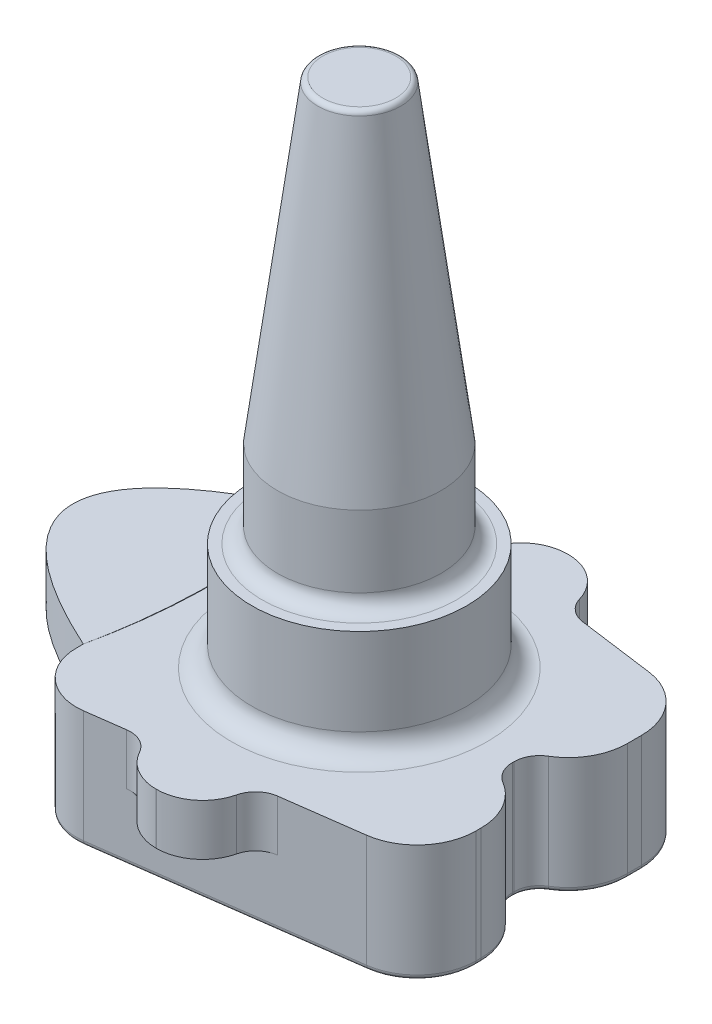
SolidWorks part; units mm, degrees
ref_plane "Plano frontal" through (0, 0, 0) normal (0, 0, 1) x (1, 0, 0)
ref_plane "Plano superior" through (0, 0, 0) normal (0, 1, 0) x (1, 0, 0)
ref_plane "Plano direito" through (0, 0, 0) normal (1, 0, 0) x (0, 0, -1)
sketch "Esboço1" plane through (0, 0, 0) normal (0, 0, 1) x (1, 0, 0)
  line L0 (17.3846, 86.7357) -> (17.3846, -75.0236) construction
  line L1 (17.3846, 86.7357) -> (25.3846, 86.7357)
  line L2 (25.3846, 86.7357) -> (33.3846, 24.7357)
  line L3 (33.3846, 24.7357) -> (33.3846, 7.7357)
  line L4 (33.3846, 7.7357) -> (38.3846, 7.7357)
  line L5 (38.3846, 7.7357) -> (38.3846, -13.2643)
  line L6 (38.3846, -13.2643) -> (97.3846, -13.2643)
  line L7 (97.3846, -13.2643) -> (97.3846, -36.2643)
  line L8 (97.3846, -36.2643) -> (17.3846, -36.2643)
  line L9 (17.3846, 86.7357) -> (17.3846, -36.2643)
  dimension "D1" = 8
  dimension "D2" = 80
  dimension "D3" = 21
  dimension "D4" = 16
  dimension "D5" = 23
  dimension "D6" = 44
  dimension "D7" = 61
  dimension "D8" = 123
revolve "Revolução1" add sketch "Esboço1" angle 360 about L0
sketch "Esboço2" plane through (0, -36.2643, 0) normal (0, -1, 0) x (1, 0, 0)
  line L0 (-62.6154, 0) -> (17.3846, 0) construction
  line L1 (56.3846, 26.25) -> (56.3846, -26.25)
  line L2 (-13.6154, 0) -> (17.3846, 0) construction
  line L3 (-13.6154, 35.75) -> (-13.6154, -35.75)
  line L4 (-13.6154, 35.75) -> (56.3846, 26.25)
  line L5 (-13.6154, -35.75) -> (56.3846, -26.25)
  circle A0 centre (17.3846, 0) radius 80 construction
  dimension "D1" = 52.5
  dimension "D2" = 31
  dimension "D3" = 71.5
extrude "Corte-extrusão2" cut sketch "Esboço2" against normal through all flip side to cut
sketch "Esboço3" plane through (0, -36.2643, 0) normal (0, -1, 0) x (1, 0, 0)
  line L0 (-13.6154, 0) -> (-117.6154, 0) construction
  line L1 (-13.6154, 35.75) -> (-13.6154, -35.75) construction
  line L2 (-13.6154, 0) -> (-11.1154, 0) construction
  circle A0 centre (-117.6154, 0) radius 106.5
  dimension "D1" = 2.5
  dimension "D2" = 104
extrude "Corte-extrusão3" cut sketch "Esboço3" against normal through all
fillet "Filete1" radius 10 2 edges at (-13.6154, -24.7643, -35.75) (-13.6154, -24.7643, 35.75)
sketch "Esboço4" plane through (0, -36.2643, 0) normal (0, -1, 0) x (1, 0, 0)
  line L0 (56.3846, -4.25) -> (48.3846, -4.25)
  line L1 (56.3846, -26.25) -> (56.3846, 26.25) construction
  line L2 (56.3846, 4.25) -> (48.3846, 4.25)
  line L3 (-11.1154, 0) -> (75.7968, 0) construction
  line L4 (48.3846, 4.25) -> (48.3846, -4.25)
  line L5 (48.3846, -4.25) -> (48.384, -4.0765)
  line L6 (56.3846, 4.25) -> (56.3846, -4.25)
  arc A0 (-13.6154, -22.9401) -> (-13.6154, 22.9401) centre (-117.6154, 0) ccw construction
  line M4 (56.3846, -26.25) -> (56.3846, 26.25)
  dimension "D2" = 8
extrude "Corte-extrusão4" cut sketch "Esboço4" against normal through all contours L4 L3 L6 L2 | L3 L4 L0 M4 region at (52.3846, -36.2643, -2.125) region at (52.3846, -36.2643, 2.125)
fillet "Filete2" radius 11.5 1 edges at (56.3846, -24.7643, 26.25)
fillet "Filete3" radius 11.5 1 edges at (56.3846, -24.7643, 4.25)
fillet "Filete4" radius 5 1 edges at (48.3846, -24.7643, 4.25)
fillet "Filete5" radius 5 1 edges at (48.3846, -24.7643, -4.25)
fillet "Filete6" radius 11.5 2 edges at (56.3846, -24.7643, -26.25) (56.3846, -24.7643, -4.25)
fillet "Filete7" radius 4 1 edges at (-3.6154, -13.2643, 0)
fillet "Filete8" radius 3 1 edges at (1.3846, 7.7357, 0)
fillet "Filete10" radius 1 16 edges at (-10.1938, -36.2643, -31.8327) (-13.6154, -36.2643, -23.6207) (-11.1154, -36.2643, 0) (-13.6154, -36.2643, 23.6207) (-10.1938, -36.2643, 31.8327) (22.0803, -36.2643, 30.9056) (53.5459, -36.2643, 23.7705) (56.3846, -36.2643, 15.7049) (54.8941, -36.2643, 9.5422) (49.0327, -36.2643, 3.5241) (48.3846, -36.2643, 0.9062) (49.0327, -36.2643, -1.7118) (54.8941, -36.2643, -7.7299) (56.3846, -36.2643, -14.7987) (53.5459, -36.2643, -23.7705) (22.0803, -36.2643, -30.9056)
sketch "Esboço5" plane through (0, -36.2643, 0) normal (0, -1, 0) x (1, 0, 0)
  line L0 (-10.1154, 0) -> (47.3846, 0.75) construction
  arc A0 (-12.6154, -23.0489) -> (-12.6154, 23.0489) centre (-117.6154, 0) ccw construction
  circle A1 centre (18.6346, 0.375) radius 20.5
  dimension "D1" = 41
extrude "Corte-extrusão6" cut sketch "Esboço5" against normal blind 2.5
chamfer "Chanfro1" distance 2 angle 45 1 edges at (39.1346, -33.7643, 0.375)
sketch "Esboço6" plane through (0, -33.7643, 0) normal (0, -1, 0) x (1, 0, 0)
  line L0 (0, 0) -> (18.6346, 0.375) construction
  line L1 (13.6346, 10.375) -> (23.6346, -9.625) construction
  line L2 (13.6346, 10.375) -> (23.6346, 10.375)
  line L3 (13.6346, 10.375) -> (13.6346, -9.625)
  line L4 (13.6346, -9.625) -> (23.6346, -9.625)
  line L5 (23.6346, 10.375) -> (23.6346, -9.625)
  dimension "D1" = 10
  dimension "D2" = 20
extrude "Corte-extrusão7" cut sketch "Esboço6" against normal blind 10
chamfer "Chanfro2" distance 1 angle 45 4 edges at (18.6346, -33.7643, -9.625) (23.6346, -33.7643, 0.375) (13.6346, -33.7643, 0.375) (18.6346, -33.7643, 10.375)
sketch "Esboço7" plane through (0, -36.2643, 0) normal (0, -1, 0) x (1, 0, 0)
  line L0 (18.6346, 0.375) -> (18.6346, 40.375) construction
  line L3 (9.1423, 40.375) -> (27.1423, 40.375)
  line L4 (9.1423, 40.375) -> (9.1423, 32.6615)
  line L5 (-2.2705, 34.2103) -> (46.4312, 27.6008) construction
  line L6 (9.1423, 32.6615) -> (27.1423, 30.2186)
  line L7 (27.1423, 30.2186) -> (27.1423, 40.375)
  line L8 (18.6346, 0.375) -> (71.2498, 0.375) construction
  line L9 (18.6346, 0.375) -> (18.6346, -39.625) construction
  line L10 (9.6346, -39.625) -> (27.6346, -39.625)
  line L11 (9.6346, -39.625) -> (9.6346, -32.5946)
  line L12 (46.4312, -27.6008) -> (-2.2705, -34.2103) construction
  line L13 (9.6346, -32.5946) -> (27.6346, -30.1518)
  line L14 (27.6346, -30.1518) -> (27.6346, -39.625)
  dimension "D1" = 40
  dimension "D2" = 18
  dimension "D3" = 40
  dimension "D4" = 18
extrude "Ressalto-extrusão2" add sketch "Esboço7" against normal blind 23
sketch "Esboço8" plane through (0, -36.2643, 0) normal (0, -1, 0) x (1, 0, 0)
  line L1 (27.1423, 40.375) -> (9.1423, 40.375) construction
  line L2 (9.1423, 40.375) -> (9.1423, 32.6615) construction
  line L3 (9.1423, 40.375) -> (27.1423, 40.375)
  line L5 (27.1423, 30.2186) -> (27.1423, 40.375) construction
  line L6 (27.1423, 30.2186) -> (9.1423, 32.6615)
  line L8 (9.1423, 32.6615) -> (9.1423, 44.4525)
  line L9 (9.1423, 44.4525) -> (27.1423, 44.2335)
  line L10 (27.1423, 44.2335) -> (27.1423, 30.2186)
  line M1 (9.1423, 40.375) -> (9.1423, 32.6615)
  line M2 (9.1423, 32.6615) -> (27.1423, 30.2186)
  line M3 (27.1423, 30.2186) -> (27.1423, 40.375)
  line M4 (27.1423, 40.375) -> (9.1423, 40.375)
extrude "Corte-extrusão10" cut sketch "Esboço8" against normal blind 13 contours M4 M1 M2 M3 region at (18.5524, -36.2643, 35.8797)
sketch "Esboço9" plane through (0, -36.2643, 0) normal (0, -1, 0) x (1, 0, 0)
  line L0 (9.6346, -32.5946) -> (9.6346, -45.9068)
  line L1 (27.6346, -30.1518) -> (27.9806, -45.9068)
  line L2 (27.9806, -45.9068) -> (9.6346, -45.9068)
  line L3 (9.6346, -32.5946) -> (27.6346, -30.1518)
extrude "Corte-extrusão11" cut sketch "Esboço9" against normal blind 13
fillet "Filete11" radius 9 2 edges at (9.1423, -18.2643, 40.375) (27.1423, -18.2643, 40.375)
fillet "Filete12" radius 5 1 edges at (27.1423, -18.2643, 30.2186)
fillet "Filete15" radius 5 1 edges at (9.1423, -18.2643, 32.6615)
fillet "Filete16" radius 9 2 edges at (9.6346, -18.2643, -39.625) (27.6346, -18.2643, -39.625)
fillet "Filete17" radius 5 1 edges at (27.6346, -18.2643, -30.1518)
fillet "Filete18" radius 5 1 edges at (9.6346, -18.2643, -32.5946)
sketch "Esboço10" plane through (0, -36.2643, 0) normal (0, -1, 0) x (1, 0, 0)
  line L0 (24.6346, 0.375) -> (12.6346, 0.375) construction
  line L1 (24.6346, 11.375) -> (24.6346, -10.625) construction
  line L2 (12.6346, -10.625) -> (12.6346, 11.375) construction
  line L3 (18.6346, 0.375) -> (-38.3654, 0.375) construction
  spline S0 degree 2 poles (-13.6154, 22.9401) (-63.1182, 0.4035) (-13.6154, -22.9401) knots 0 0 0 1 1 1
  spline S1 degree 2 poles (-13.6154, 22.9401) (-8.7851, 0.0082) (-13.6154, -22.9401) knots 0 0 0 1 1 1
  dimension "D1" = 57
extrude "Ressalto-extrusão4" add sketch "Esboço10" against normal blind 23 separate body
sketch "Esboço11" plane through (0, -36.2643, 0) normal (0, -1, 0) x (1, 0, 0)
  line L0 (0, 0) -> (-45.2937, 0) construction
  line L1 (-13.6154, -22.9401) -> (-48.3557, -22.9401)
  line L2 (-48.3557, -22.9401) -> (-48.3557, 22.9401)
  line L3 (-48.3557, 22.9401) -> (-13.6154, 22.9401)
  spline S0 degree 2 poles (-13.6154, 22.9401) (-8.6512, 0) (-13.6154, -22.9401) knots 0 0 0 1 1 1
extrude "Corte-extrusão12" cut sketch "Esboço11" against normal blind 13
fillet "Filete20" radius 1 1 edges at (9.3846, 86.7357, 0)
